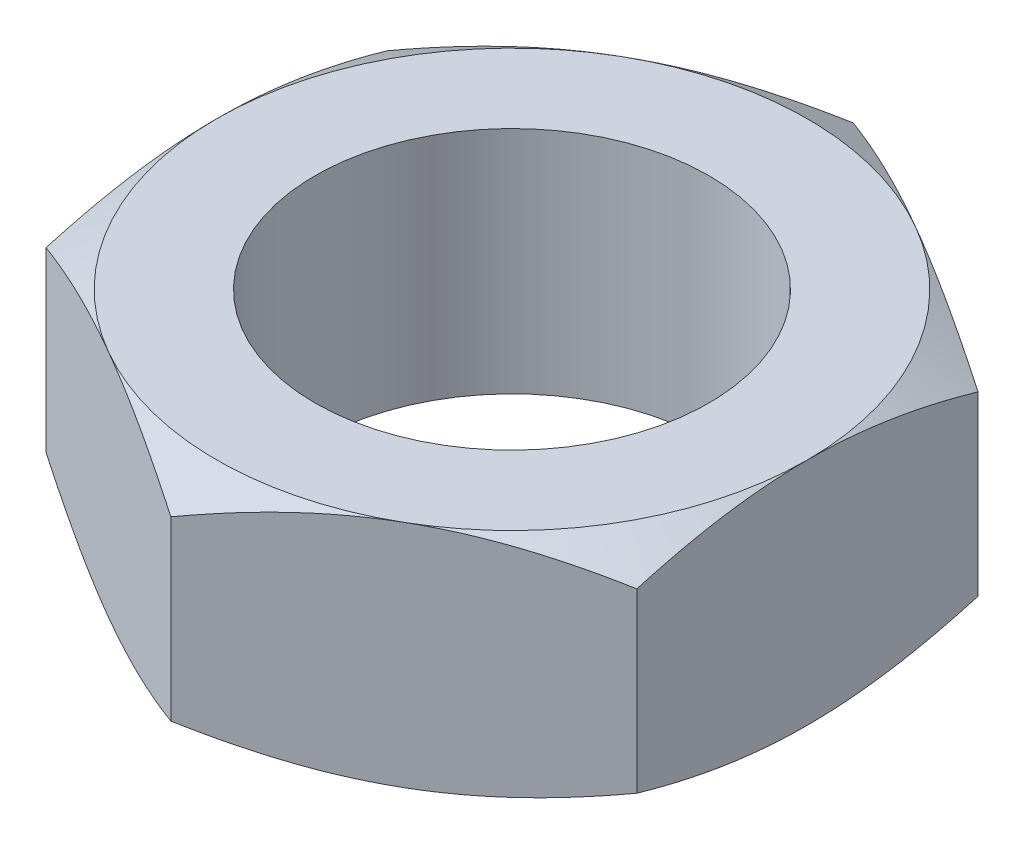
SolidWorks part; units mm, degrees
material "Alloy Steel"
ref_plane "Front Plane" through (0, 0, 0) normal (0, 0, 1) x (1, 0, 0)
ref_plane "Top Plane" through (0, 0, 0) normal (0, 1, 0) x (1, 0, 0)
ref_plane "Right Plane" through (0, 0, 0) normal (1, 0, 0) x (0, 0, -1)
sketch "Sketch1" plane through (0, 0, 0) normal (0, 1, 0) x (1, 0, 0)
  line L1 (-7.1438, 4.1244) -> (-7.1438, -4.1244)
  line L2 (-7.1438, -4.1244) -> (0, -8.2489)
  line L3 (0, -8.2489) -> (7.1437, -4.1244)
  line L4 (7.1437, -4.1244) -> (7.1437, 4.1244)
  line L5 (7.1437, 4.1244) -> (0, 8.2489)
  line L6 (0, 8.2489) -> (-7.1438, 4.1244)
  circle A0 centre (0, 0) radius 7.1438 construction
  circle A1 centre (0, 0) radius 4.7625
  dimension "Thread Size" = 9.525
  dimension "Hex" = 14.2875
extrude "Boss-Extrude1" add sketch "Sketch1" along normal mid plane 5.5562
sketch "Sketch2" plane through (0, 2.7781, 0) normal (0, 1, 0) x (1, 0, 0)
  circle A0 centre (0, 0) radius 4.7625 construction
  circle A1 centre (0, 0) radius 4.7625
curve "Helix/Spiral1" [suppressed] pitch 1.0583 height 6.6146 turns 6.25 parameters "Pitch"=1.0583
sketch "Sketch3" plane through (0, 0, 0) normal (1, 0, 0) x (0, 0, -1)
  line L0 (4.0751, 3.3073) -> (4.7625, 3.7042)
  line L1 (4.7625, 3.7042) -> (4.7625, 2.7781)
  line L2 (4.7625, 2.7781) -> (4.0751, 3.175)
  line L3 (4.0751, 3.175) -> (4.0751, 3.3073)
  line L4 (4.4188, 3.5057) -> (4.4188, 2.9766) construction
  line L5 (4.0751, 3.2411) -> (4.7625, 3.2411) construction
  line L6 (4.7625, 2.7781) -> (-4.7625, 2.7781) construction
  dimension "D1" = 60
  dimension "D2" = 0.1323
  dimension "D3" = 0.5292
sweep "Sweep1" [suppressed] add profiles "Sketch3" path "Helix/Spiral1"
sketch "Sketch4" plane through (0, 2.7781, 0) normal (0, 1, 0) x (1, 0, 0)
  circle A1 centre (0, 0) radius 4.7625
  circle A2 centre (0, 0) radius 4.7625
  dimension "D1" = 0
extrude "Cut-Extrude1" [suppressed] cut sketch "Sketch4" along normal through all and the other way through all draft 45
sketch "Sketch5" plane through (0, 2.7781, 0) normal (0, 1, 0) x (1, 0, 0)
  circle A0 centre (0, 0) radius 7.1438 construction
  circle A1 centre (0, 0) radius 7.1438
extrude "Cut-Extrude2" cut sketch "Sketch5" against normal through all draft 60 flip side to cut
mirror "Mirror1" about plane through (0, 0, 0) normal (0, 1, 0) of "Cut-Extrude2", "Cut-Extrude1"
equation "\"D2@Sketch3\" = \"Pitch@Helix/Spiral1\"*.125"
equation "\"D3@Sketch3\" = \"Pitch@Helix/Spiral1\"*.5"
equation "\"D3@Helix/Spiral1\" = \"Height@Boss-Extrude1\"+\"Pitch@Helix/Spiral1\""
